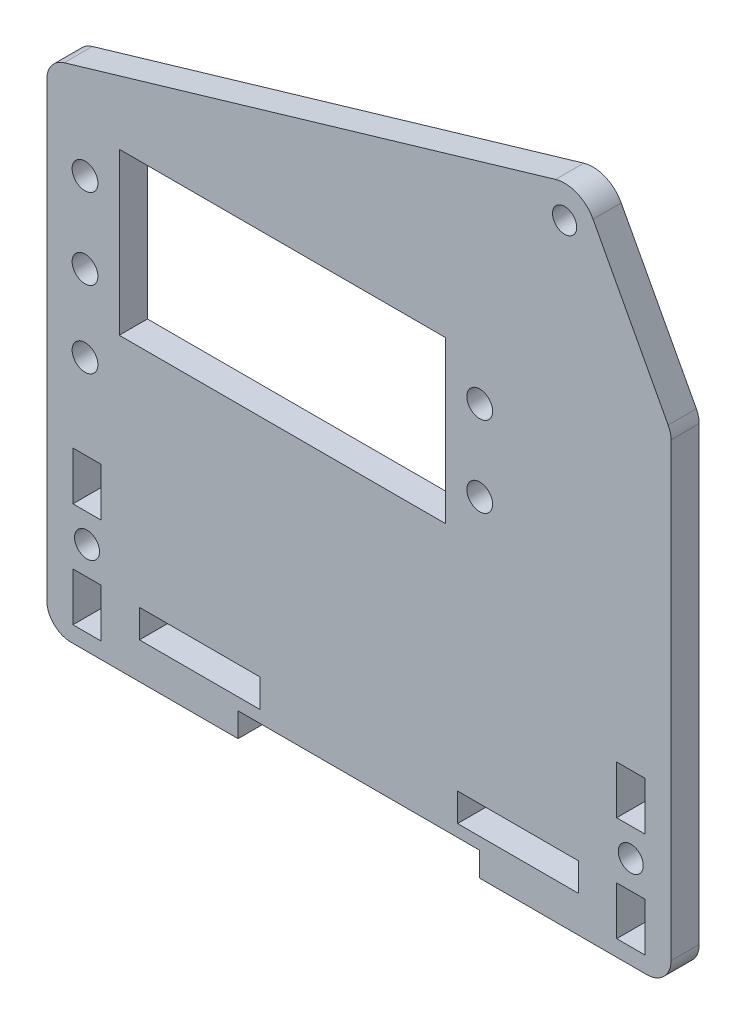
SolidWorks part; units mm, degrees
material "Balsa"
ref_plane "Front Plane" through (0, 0, 0) normal (0, 0, 1) x (1, 0, 0)
ref_plane "Top Plane" through (0, 0, 0) normal (0, 1, 0) x (1, 0, 0)
ref_plane "Right Plane" through (0, 0, 0) normal (1, 0, 0) x (0, 0, -1)
sketch "Sketch1" plane through (0, 0, 0) normal (0, 0, 1) x (1, 0, 0)
  line L0 (27.5074, 45) -> (23.5724, 45) construction
  line L1 (-35.75, -31) -> (35.75, -31)
  line L2 (-38.75, -28) -> (-38.75, 28)
  line L3 (-36.1824, 31) -> (36.1824, 31) construction
  line L4 (38.75, -28) -> (38.75, 28)
  line L5 (0, 31) -> (0, -31) construction
  line L6 (-38.75, 0) -> (38.75, 0) construction
  line L7 (-29.75, 5) -> (10.75, 5)
  line L8 (-29.75, 5) -> (-29.75, 25)
  line L9 (-29.75, 25) -> (10.75, 25)
  line L10 (10.75, 5) -> (10.75, 25)
  line L11 (25.5399, 54.2026) -> (25.5399, 47.4582) construction
  line L12 (24.4103, 48.8372) -> (-36.5972, 30.8779)
  line L13 (29.0685, 46.8839) -> (38.3964, 29.413)
  line L14 (10.75, 15) -> (-29.75, 15) construction
  line L15 (-19.36, 18.0838) -> (-19.36, 11.9162) construction
  arc A0 (38.3964, 29.413) -> (38.75, 28) centre (35.75, 28) cw
  arc A1 (35.75, -31) -> (38.75, -28) centre (35.75, -28) ccw
  arc A2 (-35.75, -31) -> (-38.75, -28) centre (-35.75, -28) cw
  arc A3 (-38.75, 28) -> (-36.5972, 30.8779) centre (-35.75, 28) cw
  circle A4 centre (25.5399, 45) radius 1.5
  arc A5 (24.4103, 48.8372) -> (29.0685, 46.8839) centre (25.5399, 45) cw
  point P0 (0, 0)
  point P8 (38.75, -31)
  point P12 (-38.75, -31)
  point P33 (-19.36, 15)
  dimension "D2" = 3
  dimension "D3" = 62
  dimension "D10" = 3
  dimension "D11" = 4
  dimension "D1" = 28
  dimension "D4" = 40.5
  dimension "D5" = 20
  dimension "D6" = 9
  dimension "D7" = 6
  dimension "D8" = 54
  dimension "D9" = 20
  dimension "D12" = 10.39
extrude "Boss-Extrude1" add sketch "Sketch1" along normal blind 3.5
sketch "Sketch2" plane through (0, 0, 0) normal (0, 0, -1) x (-1, 0, 0)
  line L0 (-38.75, -19.5) -> (38.75, -19.5) construction
  line L1 (-38.75, -28) -> (-38.75, 28) construction
  line L2 (38.75, 28) -> (38.75, -28) construction
  line L3 (35.75, -31) -> (-35.75, -31) construction
  line L4 (-33.75, -8) -> (-33.75, -31) construction
  line L5 (0, 9.9619) -> (0, -7.9273) construction
  line L6 (-35.5, -16) -> (-32, -16)
  line L7 (-35.5, -16) -> (-35.5, -10)
  line L8 (-35.5, -10) -> (-32, -10)
  line L9 (-32, -16) -> (-32, -10)
  line L10 (-33.75, -10) -> (-33.75, -16) construction
  line L11 (-35.5, -13) -> (-32, -13) construction
  line L12 (-35.5, -29) -> (-32, -29)
  line L13 (-35.5, -29) -> (-35.5, -23)
  line L14 (-35.5, -23) -> (-32, -23)
  line L15 (-32, -29) -> (-32, -23)
  line L16 (-33.75, -23) -> (-33.75, -29) construction
  line L17 (-35.5, -26) -> (-32, -26) construction
  line L18 (35.5, -29) -> (32, -29)
  line L19 (35.5, -29) -> (35.5, -23)
  line L20 (35.5, -23) -> (32, -23)
  line L21 (32, -29) -> (32, -23)
  line L22 (35.5, -16) -> (32, -16)
  line L23 (35.5, -16) -> (35.5, -10)
  line L24 (35.5, -10) -> (32, -10)
  line L25 (32, -16) -> (32, -10)
  circle A0 centre (-33.75, -19.5) radius 1.55
  circle A1 centre (33.75, -19.5) radius 1.55
  point P10 (-33.75, -13)
  point P14 (-33.75, -26)
  dimension "D8" = 3.1
  dimension "D1" = 11.5
  dimension "D2" = 5
  dimension "D3" = 3.5
  dimension "D4" = 6
  dimension "D5" = 6
  dimension "D6" = 19
  dimension "D9" = 0
extrude "Cut-Extrude1" cut sketch "Sketch2" against normal through all
sketch "Sketch3" plane through (0, 0, 0) normal (0, 0, -1) x (-1, 0, 0)
  line L0 (-32, -23) -> (32, -23) construction
  line L1 (0, 0) -> (0, -31.4864) construction
  line L2 (27.25, -23) -> (27.25, -26.5)
  line L3 (-27.25, -23) -> (-12.25, -23)
  line L4 (-27.25, -23) -> (-27.25, -26.5)
  line L5 (-27.25, -26.5) -> (-12.25, -26.5)
  line L6 (-12.25, -23) -> (-12.25, -26.5)
  line L7 (27.25, -23) -> (12.25, -23)
  line L8 (12.25, -23) -> (12.25, -26.5)
  line L9 (27.25, -26.5) -> (12.25, -26.5)
  dimension "D1" = 24.5
  dimension "D2" = 15
  dimension "D3" = 3.5
extrude "Cut-Extrude2" cut sketch "Sketch3" against normal through all
sketch "Sketch4" plane through (0, 0, 0) normal (0, 0, -1) x (-1, 0, 0)
  line L0 (-15, 15) -> (29.75, 15) construction
  line L1 (9.5, 28.7883) -> (9.5, -1.2827) construction
  line L2 (-10.75, 25) -> (29.75, 25) construction
  line L3 (29.75, 5) -> (-10.75, 5) construction
  line L4 (29.75, 25) -> (29.75, 5) construction
  line L5 (-10.75, 5) -> (-10.75, 25) construction
  line L7 (-15, 10) -> (34, 10) construction
  line L8 (-15, 10) -> (-15, 20) construction
  line L9 (-15, 20) -> (34, 20) construction
  line L10 (34, 10) -> (34, 20) construction
  line L11 (9.5, 20) -> (9.5, 10) construction
  line L12 (-15, 15) -> (34, 15) construction
  circle A0 centre (-15, 20) radius 1.6
  circle A1 centre (-15, 10) radius 1.6
  circle A2 centre (34, 10) radius 1.6
  circle A3 centre (34, 20) radius 1.6
  point P12 (9.5, 15)
  dimension "D3" = 3.2
  dimension "D1" = 10
  dimension "D2" = 49
extrude "Cut-Extrude3" cut sketch "Sketch4" against normal through all
sketch "Sketch5" plane through (0, 0, 0) normal (0, 0, -1) x (-1, 0, 0)
  line L0 (34, -31) -> (34, 31.6425) construction
  line L3 (35.75, -31) -> (-35.75, -31) construction
  line L4 (-24.4103, 48.8372) -> (36.5972, 30.8779) construction
  circle A0 centre (34, 0.5) radius 1.6
  circle A8 centre (34, 20) radius 1.6 construction
  circle A10 centre (34, 20) radius 1.6
  circle A11 centre (34, 10) radius 1.6 construction
  circle A12 centre (34, 10) radius 1.6
  dimension "D1" = 2
extrude "Cut-Extrude5" cut sketch "Sketch5" against normal up to next contours A0
sketch "Sketch6" plane through (0, 0, 3.5) normal (0, 0, 1) x (1, 0, 0)
  line L0 (0, 9.3086) -> (0, -38.9466) construction
  line L1 (-35.75, -31) -> (35.75, -31) construction
  line L2 (-15, -28) -> (15, -28)
  line L3 (-15, -28) -> (-15, -31)
  line L4 (-15, -31) -> (15, -31)
  line L5 (15, -28) -> (15, -31)
  line L6 (-15, -28) -> (15, -31) construction
  line L7 (-15, -31) -> (15, -28) construction
  point P3 (0, -29.5)
  dimension "D1" = 3
  dimension "D2" = 30
extrude "Cut-Extrude6" cut sketch "Sketch6" against normal blind 10
